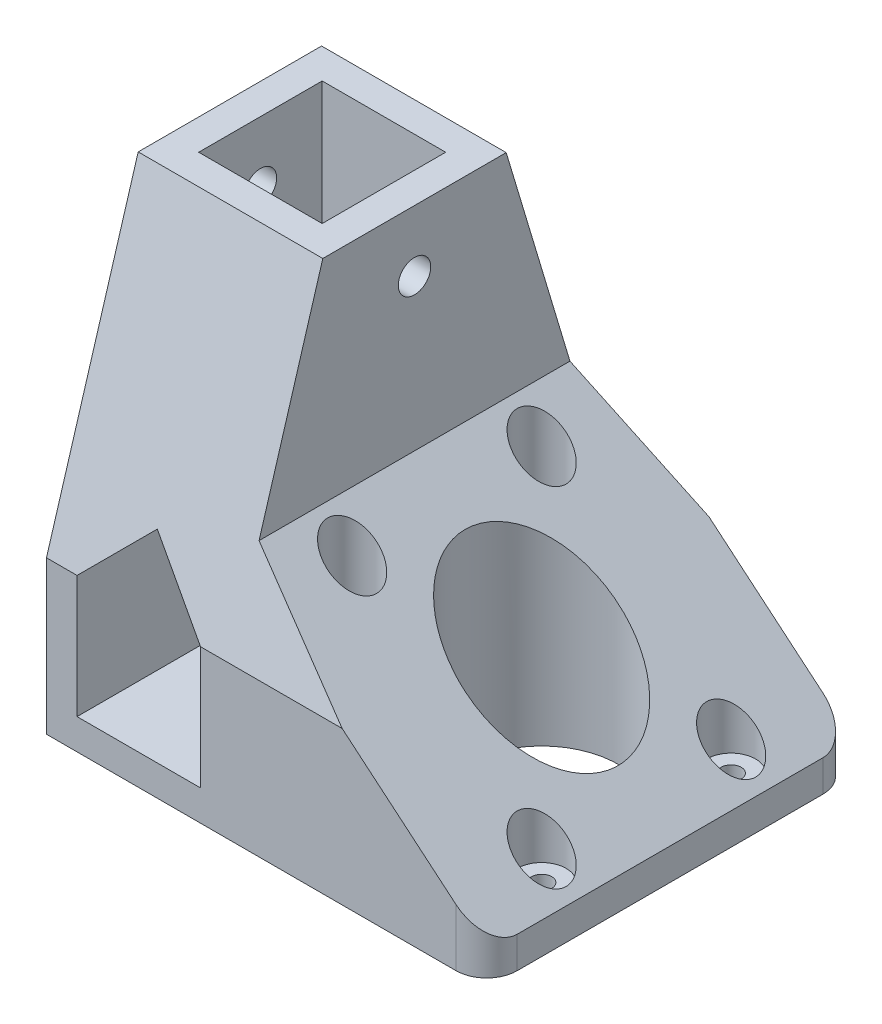
SolidWorks part; units mm, degrees
ref_plane "Front Plane" through (0, 0, 0) normal (0, 0, 1) x (1, 0, 0)
ref_plane "Top Plane" through (0, 0, 0) normal (0, 1, 0) x (1, 0, 0)
ref_plane "Right Plane" through (0, 0, 0) normal (1, 0, 0) x (0, 0, -1)
sketch "Sketch1" plane through (0, 0, 0) normal (0, 1, 0) x (1, 0, 0)
  line L1 (0, 0) -> (72, 0)
  line L2 (0, 0) -> (0, 60)
  line L3 (0, 60) -> (72, 60)
  line L4 (72, 0) -> (72, 60)
  dimension "D1" = 72
  dimension "D2" = 60
extrude "Boss-Extrude1" add sketch "Sketch1" along normal blind 5
sketch "Sketch2" plane through (0, 5, 0) normal (0, 1, 0) x (1, 0, 0)
  line L0 (0, 0) -> (72, 0) construction
  line L1 (0, 60) -> (5, 60)
  line L2 (0, 60) -> (0, 0)
  line L3 (0, 0) -> (5, 0)
  line L4 (5, 60) -> (5, 0)
  dimension "D1" = 5
extrude "Boss-Extrude2" add sketch "Sketch2" along normal blind 70
sketch "Sketch3" plane through (0, 5, 0) normal (0, 1, 0) x (1, 0, 0)
  line L0 (72, 60) -> (5, 60) construction
  line L1 (25.2, 60) -> (30.2, 60)
  line L2 (25.2, 60) -> (25.2, 0)
  line L3 (25.2, 0) -> (30.2, 0)
  line L4 (30.2, 60) -> (30.2, 0)
  line L5 (5, 0) -> (72, 0) construction
  line L6 (5, 0) -> (5, 60) construction
  dimension "D1" = 5
  dimension "D2" = 20.2
extrude "Boss-Extrude3" add sketch "Sketch3" along normal blind 70
sketch "Sketch11" plane through (0, 0, -60) normal (0, 0, -1) x (-1, 0, 0)
  line L0 (-25.2, 25) -> (-15.1, 35.1)
  line L1 (-25.2, 75) -> (-25.2, 5) construction
  line L2 (-15.1, 35.1) -> (-5, 25)
  line L3 (-5, 75) -> (-5, 5) construction
  line L4 (-5, 25) -> (-5, 75)
  line L5 (-5, 75) -> (-25.2, 75)
  line L6 (-25.2, 75) -> (-25.2, 25)
  dimension "D1" = 50
  dimension "D2" = 50
  dimension "D3" = 45
  dimension "D4" = 45
extrude "Boss-Extrude4" add sketch "Sketch11" against normal up to surface (60 mm away) up to face at (26.48, 32, 0)
chamfer "Chamfer1" distance 42 angle 40 1 edges at (30.2, 5, -30) first distance on face at (51.1, 5, -30)
chamfer "Chamfer2" distance 50 angle 16.7 2 edges at (15.1, 75, -60) (15.1, 75, 0) first distance on face at (15.1, 19.02, -60) first distance on face at (15.1, 19.02, 0)
sketch "Sketch12" plane through (0, 75, 0) normal (0, 1, 0) x (1, 0, 0)
  line L0 (0, 30) -> (30.2, 30) construction
  line L1 (5, 40.1) -> (25.2, 40.1)
  line L2 (5, 40.1) -> (5, 19.9)
  line L3 (5, 19.9) -> (25.2, 19.9)
  line L4 (25.2, 40.1) -> (25.2, 19.9)
  line L5 (5, 40.1) -> (25.2, 19.9) construction
  line L6 (5, 19.9) -> (25.2, 40.1) construction
  line L8 (30.2, 4.5729) -> (30.2, 55.4271) construction
  line L9 (0, 44.9993) -> (0, 15.0007) construction
  point P0 (15.1, 30)
  point P8 (15.2, 30)
  point P9 (15.1, 30)
  dimension "D1" = 20.2
  dimension "D2" = 20.2
  dimension "D3" = 5
extrude "Cut-Extrude8" cut sketch "Sketch12" against normal blind 67
sketch "Sketch5" plane through (0, 5, 0) normal (0, 1, 0) x (1, 0, 0)
  line L0 (72, 0) -> (72, 60) construction
  line L1 (5, 0) -> (25.2, 0) construction
  circle A0 centre (51, 30) radius 12.5
  dimension "D1" = 25
  dimension "D2" = 21
  dimension "D3" = 30
extrude "Cut-Extrude1" cut sketch "Sketch5" against normal through all both and the other way through all
sketch "Sketch6" plane through (0, 0, 0) normal (0, -1, 0) x (1, 0, 0)
  line L1 (35.5, -14.5) -> (66.5, -14.5) construction
  line L2 (35.5, -14.5) -> (35.5, -45.5) construction
  line L3 (35.5, -45.5) -> (66.5, -45.5) construction
  line L4 (66.5, -14.5) -> (66.5, -45.5) construction
  line L5 (35.5, -14.5) -> (66.5, -45.5) construction
  line L6 (35.5, -45.5) -> (66.5, -14.5) construction
  circle A0 centre (66.5, -14.5) radius 1.65
  circle A1 centre (66.5, -45.5) radius 1.65
  circle A2 centre (35.5, -45.5) radius 1.65
  circle A3 centre (35.5, -14.5) radius 1.65
  point P0 (51, -30)
  dimension "D3" = 3.3
  dimension "D1" = 31
  dimension "D2" = 31
extrude "Cut-Extrude2" cut sketch "Sketch6" against normal through all
sketch "Sketch7" plane through (0, 5, 0) normal (0, 1, 0) x (1, 0, 0)
  circle A0 centre (66.5, 45.5) radius 4
  circle A1 centre (66.5, 14.5) radius 4
  circle A2 centre (35.5, 14.5) radius 4
  circle A4 centre (35.5, 45.5) radius 4
  dimension "D1" = 8
extrude "Cut-Extrude4" cut sketch "Sketch7" along normal through all
sketch "Sketch8" plane through (30.2, 0, 0) normal (1, 0, 0) x (0, 0, -1)
  line L0 (15.0007, 75) -> (44.9993, 75) construction
  line L1 (30, 75) -> (30, 40.2422) construction
  line L2 (4.5729, 40.2422) -> (55.4271, 40.2422) construction
  circle A0 centre (30, 65) radius 2.65
  dimension "D1" = 5.3
  dimension "D2" = 10
extrude "Cut-Extrude5" cut sketch "Sketch8" against normal through all both and the other way through all
sketch "Sketch9" plane through (0, 0, 0) normal (0, -1, 0) x (1, 0, 0)
  line L1 (0, -60) -> (0, 0) construction
  line L2 (0, -30) -> (72, -30) construction
  line L3 (72, 0) -> (72, -60) construction
  circle A0 centre (15, -30) radius 2.65
  dimension "5.3" = 5.3
  dimension "D2" = 15
extrude "Cut-Extrude6" cut sketch "Sketch9" against normal through all both and the other way through all contours A0
fillet "Fillet1" radius 5 2 edges at (72, 2.5839, -60) (72, 2.5839, 0)
sketch "Sketch10" plane through (0, 0, 0) normal (-1, 0, 0) x (0, 0, 1)
  line L0 (-60, 0) -> (0, 0) construction
  line L1 (0, 25) -> (0, 0) construction
  circle A0 centre (-30, 15) radius 2.65
  dimension "D3" = 5.3
  dimension "D1" = 15
  dimension "D2" = 30
extrude "Cut-Extrude7" cut sketch "Sketch10" against normal blind 10
